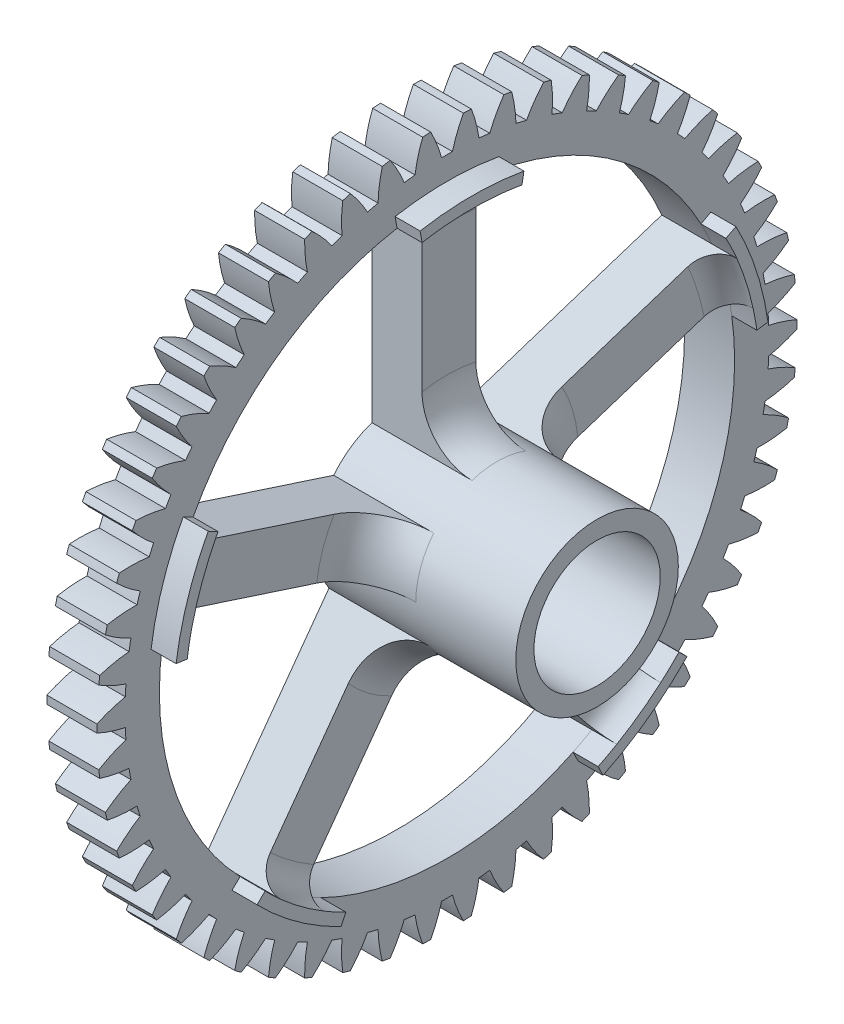
SolidWorks part; units mm, degrees
ref_plane "Plane1" through (0, 0, 0) normal (0, 0, 1) x (1, 0, 0)
ref_plane "Plane2" through (0, 0, 0) normal (0, 1, 0) x (1, 0, 0)
ref_plane "Plane3" through (0, 0, 0) normal (1, 0, 0) x (0, 0, -1)
other "Configuration Table"
sketch "HoldingSke" plane through (0, 0, 0) normal (0, 1, 0) x (1, 0, 0)
  line L0 (0, 0) -> (1.1756, -1.618)
  line L1 (-15, 0) -> (100, 0) construction
  line L2 (0, 0) -> (-2.1039, 2.3779)
  line L3 (0, 0) -> (-11.863, 4.5341)
  line L4 (0, 0) -> (5.0761, 6.9867)
  line L5 (0, 0) -> (-46.8476, -17.4728)
  line L6 (0, 0) -> (-1.6579, -1.1186)
  line L7 (-2.1039, 2.3779) -> (8.6586, 51.2059)
  line L8 (-76.2, 54.61) -> (-76.1, 54.61)
  line L9 (-71.009, 38.7566) -> (-53.1078, 45.2721)
  line L10 (-76.2, 71.12) -> (104.1128, 71.12)
  line L11 (0, 0) -> (-2, 0)
  line L12 (-76.2, 101.6) -> (-76.181, 101.6)
  line L13 (24.9733, 27.94) -> (52.9518, 28.4284)
  line L14 (24.9733, 27.94) -> (24.9743, 27.94)
  line L15 (24.9733, 27.94) -> (100.4006, 29.5858)
  line L16 (-63.627, -0.5) -> (-12.827, -0.5)
  circle A0 centre (0, 0) radius 0.5
  circle A1 centre (0, 0) radius 12.874
  circle A2 centre (0, 0) radius 37.5
  circle A3 centre (0, 0) radius 0.5
  dimension "Num_teeth" = 54
  dimension "Pitch_radius" = 180.3128
  dimension "Width" = 2
  dimension "Thickness" = 2
sketch "BasProSke" plane through (0, 0, 0) normal (0, 1, 0) x (1, 0, 0)
  line L0 (-10, 0) -> (60, 0) construction
  line L1 (0, 0) -> (0, 14)
  line L2 (0, 0) -> (2, 0)
  line L3 (2, 0) -> (2, 14)
  line L4 (2, 14) -> (0, 14)
  dimension "Thickness" = 2
  dimension "Diameter" = 28
revolve "Base-Revolve" add sketch "BasProSke" angle 360 about L0
sketch "TooCutSke" plane through (0, 0, 0) normal (1, 0, 0) x (0, 0, -1)
  line L1 (0, 0) -> (0, 107) construction
  line L2 (0, 0) -> (-0.4259, 13.4933) construction
  line L3 (0, 0) -> (-1.5694, 26.9448) construction
  line L4 (-0.4259, 13.4933) -> (-0.7847, 13.4724) construction
  arc A0 (0.217, 12.8722) -> (-0.217, 12.8722) centre (0, 0) ccw
  arc A1 (0.6676, 14.0095) -> (-0.6676, 14.0095) centre (0, 0) ccw
  circle A2 centre (0, 0) radius 13.5 construction
  circle A3 centre (0, 0) radius 12.6859 construction
  arc A4 (-0.217, 12.8722) -> (-0.6676, 14.0095) centre (-5.4304, 11.4648) ccw
  arc A5 (0.6676, 14.0095) -> (0.217, 12.8722) centre (5.4304, 11.4648) ccw
extrude "ToothCut" cut sketch "TooCutSke" along normal through all
fillet "Breaks" [suppressed] radius 0.01 tangent propagation no
fillet "RootFillets" [suppressed] radius 0.126
pattern_circular "TeethCuts" count 54 every 6.667 about axis through (-10, 0, 0) along (1, 0, 0) of "ToothCut", "RootFillets", "Breaks"
sketch "HubNeaOneSke" plane through (0, 0, 0) normal (-1, 0, 0) x (0, 0, 1)
  circle A0 centre (0, 0) radius 12.874
  dimension "Diameter" = 25.748
extrude "HubNearOne" [suppressed] add sketch "HubNeaOneSke" along normal blind 48.0001
sketch "HubNeaBotSke" plane through (0, 0, 0) normal (-1, 0, 0) x (0, 0, 1)
  circle A0 centre (0, 0) radius 12.874
  dimension "Diameter" = 25.748
extrude "HubNearBoth" [suppressed] add sketch "HubNeaBotSke" along normal blind 24
ref_plane "FarPln" through (2, 0, 0) normal (1, 0, 0) x (0, 0, -1)
sketch "HubFarSke" plane through (2, 0, 0) normal (1, 0, 0) x (0, 0, -1)
  circle A0 centre (0, 0) radius 12.874
  dimension "Diameter" = 25.748
extrude "HubFar" [suppressed] add sketch "HubFarSke" along normal blind 24
sketch "BorSke" plane through (0, 0, 0) normal (1, 0, 0) x (0, 0, -1)
  circle A0 centre (0, 0) radius 0.5
extrude "Bore" cut sketch "BorSke" along normal mid plane 100.0001
sketch "KeySke" plane through (0, 0, 0) normal (1, 0, 0) x (0, 0, -1)
  line L0 (-0.05, 0) -> (-0.05, 0.6)
  line L1 (-0.05, 0.6) -> (0.05, 0.6)
  line L2 (0.05, 0.6) -> (0.05, 0)
  line L3 (0, 0) -> (0, 34) construction
  line L4 (-0.05, 0) -> (0.05, 0)
extrude "Keyway" [suppressed] cut sketch "KeySke" along normal mid plane 100.0001
pattern_circular "Keyway2" [suppressed] count 2 every 90 about axis through (-10, 0, 0) along (1, 0, 0)
sketch "草图1" plane through (0, 0, 0) normal (-1, 0, 0) x (0, 0, 1)
  line L0 (0, 0) -> (0.5, 0)
  line L1 (0.5, 3.2113) -> (0.5, 12.2398)
  line L2 (11.4151, 4.445) -> (2.8021, 1.6465)
  line L3 (-0.7, 12.23) -> (-0.7, 3.1737)
  line L4 (3.2086, 0.5168) -> (11.7952, 3.3068)
  line L5 (7.7549, -9.4828) -> (2.4318, -2.1561)
  line L6 (1.4831, -2.8919) -> (6.7899, -10.1961)
  line L7 (-6.6223, -10.3057) -> (-1.2992, -2.979)
  line L8 (-2.2921, -2.3041) -> (-7.5989, -9.6083)
  line L9 (-11.8477, 3.1135) -> (-3.2347, 0.315)
  line L10 (-2.8996, 1.4679) -> (-11.4862, 4.2578)
  circle A7 centre (0, 0) radius 12.75 construction
  circle A8 centre (0, 0) radius 2.525
  circle A9 centre (0, 0) radius 3.25
  circle A10 centre (0, 0) radius 11
  circle A11 centre (0, 0) radius 0.5 construction
  point P32 (0, 0)
  point P37 (0, 0)
  point P42 (0, 0)
  dimension "D2" = 5
sketch "草图3" plane through (2, 0, 0) normal (1, 0, 0) x (0, 0, -1)
  circle A0 centre (0, 0) radius 12.75
  circle A1 centre (0, 0) radius 12.25
sketch "草图13" plane through (2, 0, 0) normal (1, 0, 0) x (0, 0, -1)
  circle A0 centre (0, 0) radius 2.525
  circle A1 centre (0, 0) radius 3.25
extrude "凸台-拉伸1" add sketch "草图13" along normal blind 6
sketch "草图17" plane through (0, 0, 0) normal (-1, 0, 0) x (0, 0, 1)
  line L0 (1.7783, 1.7926) -> (10.8985, 4.7559)
  line L1 (11.578, 2.7104) -> (2.5141, -0.2346)
  line L2 (1, 11.8489) -> (1, 2.3185)
  line L3 (1, 0) -> (-1, 0)
  line L4 (-1.1553, 2.2452) -> (-1.1553, 11.8347)
  line L5 (2.2544, -1.1373) -> (7.891, -8.8954)
  line L6 (6.1556, -10.1737) -> (0.5538, -2.4635)
  line L7 (-0.385, -2.4955) -> (-6.0216, -10.2536)
  line L8 (-7.7736, -8.9981) -> (-2.1718, -1.288)
  line L9 (-2.4923, -0.405) -> (-11.6125, 2.5583)
  line L10 (-10.9599, 4.6126) -> (-1.896, 1.6675)
  circle A1 centre (0, 0) radius 12.55
  circle A3 centre (0, 0) radius 2.525
  circle A4 centre (0, 0) radius 3.25
  circle A5 centre (0, 0) radius 11.5
  point P27 (0, 0)
  point P36 (0, 0)
  dimension "D1" = 5
extrude "切除-拉伸1" cut sketch "草图17" against normal blind 10 contours A4 L4 A5 L10 | A4 L9 A5 L8 | A4 L7 A5 L6 | A4 L5 A5 L1 | A4 L0 A5 L2 | A3 region at (0, 0.9435, 2.2649) region at (0, 6.545, 4.6619) region at (0, -2.4113, 7.6653) region at (0, 6.4563, -4.784) region at (0, -8.0352, 0.0755) region at (0, -2.5548, -7.6186)
fillet "圆角1" radius 2 5 edges at (2, 1.0823, 3.0645) (2, 3.249, -0.0823) (2, 0.9257, -3.1154) (2, -2.6769, -1.8431) (2, -2.5801, 1.9763)
sketch "草图18" plane through (2, 0, 0) normal (1, 0, 0) x (0, 0, -1)
  line L0 (0, 0) -> (0, 11.95)
  line L1 (2.0751, 11.7685) -> (1.9969, 11.3252)
  line L11 (-2.0751, 11.7685) -> (-1.9969, 11.3252)
  line L12 (10.5512, 5.6102) -> (10.1538, 5.3989)
  line L13 (11.8337, 1.6631) -> (11.388, 1.6005)
  line L14 (8.5961, -8.3012) -> (8.2723, -7.9885)
  line L15 (5.2385, -10.7406) -> (5.0412, -10.336)
  line L16 (-5.2385, -10.7406) -> (-5.0412, -10.336)
  line L17 (-8.5961, -8.3012) -> (-8.2723, -7.9885)
  line L18 (-11.8337, 1.6631) -> (-11.388, 1.6005)
  line L19 (-10.5512, 5.6102) -> (-10.1538, 5.3989)
  arc A2 (-2.0751, 11.7685) -> (2.0751, 11.7685) centre (0, 0) cw
  arc A12 (-1.9969, 11.3252) -> (1.9969, 11.3252) centre (0, 0) cw
  arc A13 (10.5512, 5.6102) -> (11.8337, 1.6631) centre (0, 0) cw
  arc A14 (10.1538, 5.3989) -> (11.388, 1.6005) centre (0, 0) cw
  arc A15 (8.5961, -8.3012) -> (5.2385, -10.7406) centre (0, 0) cw
  arc A16 (8.2723, -7.9885) -> (5.0412, -10.336) centre (0, 0) cw
  arc A17 (-5.2385, -10.7406) -> (-8.5961, -8.3012) centre (0, 0) cw
  arc A18 (-5.0412, -10.336) -> (-8.2723, -7.9885) centre (0, 0) cw
  arc A19 (-11.8337, 1.6631) -> (-10.5512, 5.6102) centre (0, 0) cw
  arc A20 (-11.388, 1.6005) -> (-10.1538, 5.3989) centre (0, 0) cw
  point P25 (0, 0)
  dimension "D1" = 5
extrude "凸台-拉伸2" add sketch "草图18" along normal blind 1 contours A2 L1 A12 L11 | A19 L19 A20 L18 | A18 L17 A17 L16 | A15 L15 A16 L14 | A13 L13 A14 L12
fillet "圆角2" radius 1 5 edges at (2, -9.2575, 6.8224) (2, -9.3492, -6.6962) (2, 3.4794, -10.9609) (2, 3.6278, 10.9127) (2, 11.4996, -0.078)
equation "' \"Module@HoldingSke\" = 6.35"
equation "' \"Num_teeth@HoldingSke\" = 12"
equation "' \"Ap@HoldingSke\" =  20"
equation "' \"Ap@HoldingSke\" = 20"
equation "' \"Width@HoldingSke\" = 0.5 * 25.4"
equation "' \"Hub_dia@HoldingSke\"= 1 * 25.4"
equation "' \"Hub_dia@HoldingSke\" = 1 * 25.4"
equation "' \"Overall_len@HoldingSke\" = 1.0 * 25.4"
equation "' \"Bore@HoldingSke\" = 0.75 * 25.4"
equation "' \"T_dim@HoldingSke\" = 0.1 * 25.4"
equation "' \"Width@KeySke\" = 0.25 * 25.4"
equation "' \"Show_teeth@HoldingSke\" = 13"
equation "' \"Backlash@HoldingSke\" = 0.009 * 25.4"
equation "' \"Addendum_fac@HoldingSke\" = 1.0"
equation "' \"Dedendum_fac@HoldingSke\" = 1.25"
equation "' \"Dedendum_add@HoldingSke\" = 0.00005 * 25.4"
equation "' \"Clearance_fac@HoldingSke\" = 0.25"
equation "\"Pitch@HoldingSke\" = 1 / \"Module@HoldingSke\""
equation "\"Overcut_dia@TooCutSke\" = (\"Num_teeth@HoldingSke\" + 2 * \"Addendum_fac@HoldingSke\") / \"Pitch@HoldingSke\" + 0.002 * 25.4"
equation "\"Pitch_dia@TooCutSke\" = \"Num_teeth@HoldingSke\" / \"Pitch@HoldingSke\""
equation "\"Base_dia@TooCutSke\" = \"Num_teeth@HoldingSke\" / \"Pitch@HoldingSke\" * cos((\"Ap@HoldingSke\"  * 3.14159265 / 180))"
equation "\"Root_dia@TooCutSke\" = (\"Num_teeth@HoldingSke\" + 2) / \"Pitch@HoldingSke\" - 2 * (\"Addendum_fac@HoldingSke\" + \"Dedendum_fac@HoldingSke\") / \"Pitch@HoldingSke\" - \"Dedendum_add@HoldingSke\" * 2"
equation "\"Half_ang@TooCutSke\" = 180 / \"Num_teeth@HoldingSke\""
equation "\"Half_CT@TooCutSke\" = \"Num_teeth@HoldingSke\" / \"Pitch@HoldingSke\" * sin((3.14159265 / 2 / \"Num_teeth@HoldingSke\")) / 2 - 7 * \"Backlash@HoldingSke\" / 4"
equation "\"Flank_rad@TooCutSke\" = \"Num_teeth@HoldingSke\" / \"Pitch@HoldingSke\" / 5"
equation "\"Radius@RootFillets\" = \"Clearance_fac@HoldingSke\" / \"Pitch@HoldingSke\" + \"Dedendum_add@HoldingSke\""
equation "\"Break_rad@Breaks\" = 0.02 / \"Pitch@HoldingSke\""
equation "\"Thickness@HoldingSke\" = \"Width@HoldingSke\""
equation "\"OAL@HoldingSke\" = \"Thickness@HoldingSke\""
equation "\"MHD@HoldingSke\" = (\"Num_teeth@HoldingSke\" + 2) / \"Pitch@HoldingSke\" - 2 * (\"Addendum_fac@HoldingSke\" + \"Dedendum_fac@HoldingSke\")  / \"Pitch@HoldingSke\" - \"Dedendum_add@HoldingSke\" * 2"
equation "\"MBD@HoldingSke\" = (\"Num_teeth@HoldingSke\" + 2) / \"Pitch@HoldingSke\" - 2 * (\"Addendum_fac@HoldingSke\" + \"Dedendum_fac@HoldingSke\")  / \"Pitch@HoldingSke\" - \"Dedendum_add@HoldingSke\" * 2 - 0.002 * 25.4"
equation "\"MHD@HoldingSke\" = ((sgn( \"MHD@HoldingSke\" - \"Hub_dia@HoldingSke\" )-1)*( \"MHD@HoldingSke\" - \"Hub_dia@HoldingSke\" ))/-2+ \"Hub_dia@HoldingSke\""
equation "\"MBD@HoldingSke\" = ((sgn( \"MBD@HoldingSke\" - \"Bore@HoldingSke\" )-1)*( \"MBD@HoldingSke\" - \"Bore@HoldingSke\" ))/-2+ \"Bore@HoldingSke\""
equation "\"OAL@HoldingSke\" = ((sgn( \"OAL@HoldingSke\" - \"Overall_len@HoldingSke\" )+1)*( \"OAL@HoldingSke\" - \"Overall_len@HoldingSke\" ))/2 + \"Overall_len@HoldingSke\" + 0.000002 * 25.4"
equation "\"Num_teeth@TeethCuts\" = int( \"Show_teeth@HoldingSke\" ) + 1"
equation "\"Num_teeth@TeethCuts\" = ((sgn( \"Num_teeth@TeethCuts\" - \"Num_teeth@HoldingSke\" )-1)*( \"Num_teeth@TeethCuts\" - \"Num_teeth@HoldingSke\" ))/-2+ \"Num_teeth@HoldingSke\""
equation "\"Num_teeth@TeethCuts\" = ((sgn( \"Num_teeth@TeethCuts\" - 2.0)+1)*( \"Num_teeth@TeethCuts\" - 2.0))/2 +2.0"
equation "\"Angle@TeethCuts\" = 360.0 / \"Num_teeth@HoldingSke\""
equation "\"Diameter@BasProSke\" = (\"Num_teeth@HoldingSke\" + 2 * \"Addendum_fac@HoldingSke\") / \"Pitch@HoldingSke\""
equation "\"Thickness@BasProSke\"  = \"Thickness@HoldingSke\""
equation "' \"Fillet_rad@BasProSke\" =  \"Thickness@HoldingSke\" * 0.05"
equation "' \"Fillet_rad@BasProSke\" = \"Thickness@HoldingSke\" * 0.05"
equation "\"MHD@HoldingSke\" = ((sgn( \"MHD@HoldingSke\" - \"Root_dia@TooCutSke\" )-1)*( \"MHD@HoldingSke\" - \"Root_dia@TooCutSke\" ))/-2+ \"Root_dia@TooCutSke\""
equation "\"Diameter@HubNeaOneSke\" = \"MHD@HoldingSke\""
equation "\"Length@HubNearOne\" = \"OAL@HoldingSke\" - \"Thickness@BasProSke\""
equation "\"Diameter@HubNeaBotSke\" = \"MHD@HoldingSke\""
equation "\"Length@HubNearBoth\" = ( \"OAL@HoldingSke\" - \"Thickness@BasProSke\" ) / 2.0"
equation "\"Thickness@FarPln\" = \"Thickness@BasProSke\""
equation "\"Diameter@HubFarSke\" = \"MHD@HoldingSke\""
equation "\"Length@HubFar\" = ( \"OAL@HoldingSke\" - \"Thickness@BasProSke\" ) / 2.0"
equation "\"Diameter@BorSke\" = \"MBD@HoldingSke\""
equation "\"D1@Bore\" = \"OAL@HoldingSke\" * 2.0"
equation "\"D1@Keyway\" = \"OAL@HoldingSke\" * 2.0"
equation "\"Offset@KeySke\" = \"T_dim@HoldingSke\" + \"MBD@HoldingSke\" / 2.0"
